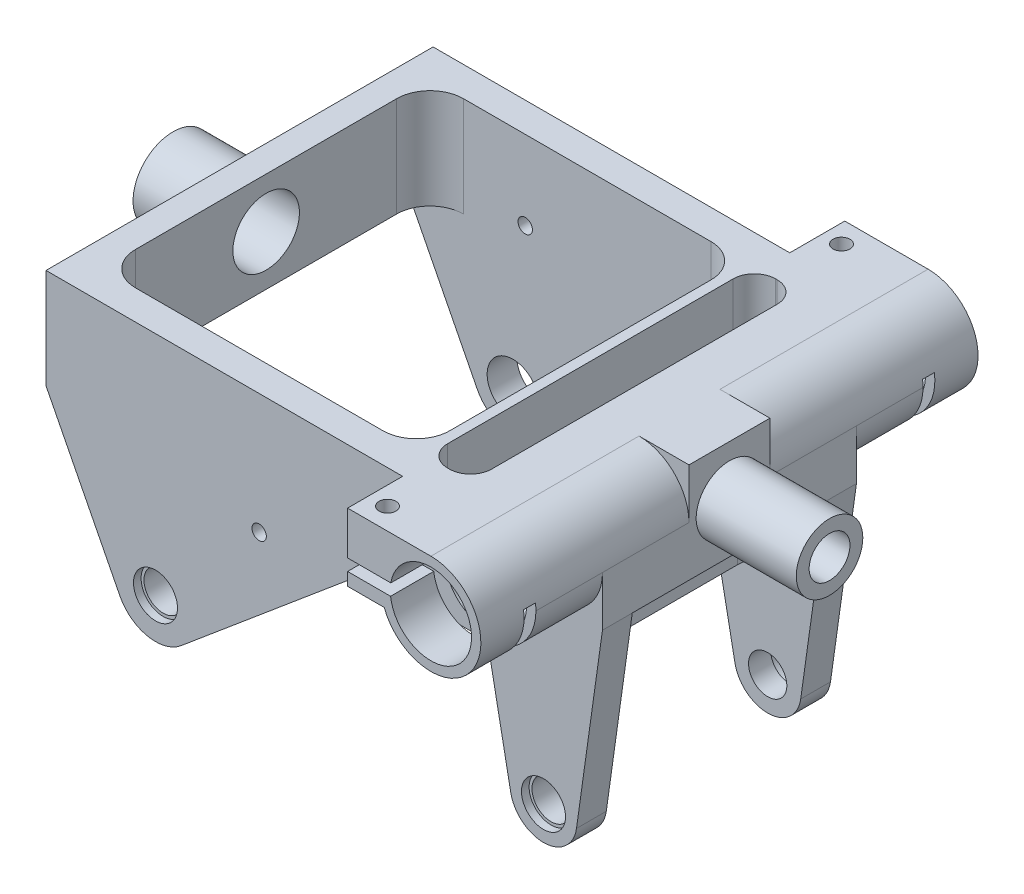
SolidWorks part; units mm, degrees
ref_plane "Front Plane" through (0, 0, 0) normal (0, 0, 1) x (1, 0, 0)
ref_plane "Top Plane" through (0, 0, 0) normal (0, 1, 0) x (1, 0, 0)
ref_plane "Right Plane" through (0, 0, 0) normal (1, 0, 0) x (0, 0, -1)
sketch "Sketch1" plane through (0, 0, 0) normal (0, 1, 0) x (1, 0, 0)
  line L0 (0, 29.0322) -> (0, -29.0322)
  line L1 (0, -29.0322) -> (73.4822, -29.0322)
  line L2 (73.4822, -29.0322) -> (73.4822, 29.0322)
  line L3 (73.4822, 29.0322) -> (0, 29.0322)
  line L4 (3.9878, 19.5872) -> (3.9878, -19.5872)
  line L5 (46.1048, 24.5872) -> (8.9878, 24.5872)
  line L6 (8.9878, -24.5872) -> (46.1048, -24.5872)
  line L7 (51.1048, 19.5872) -> (51.1048, -19.5872)
  line L8 (73.4822, 24.5872) -> (0, 24.5872) construction
  line L9 (3.9878, 29.0322) -> (3.9878, -29.0322) construction
  line L10 (51.1048, 29.0322) -> (51.1048, -29.0322) construction
  line L11 (0, -24.5872) -> (73.4822, -24.5872) construction
  arc A0 (3.9878, -19.5872) -> (8.9878, -24.5872) centre (8.9878, -19.5872) ccw
  arc A1 (46.1048, -24.5872) -> (51.1048, -19.5872) centre (46.1048, -19.5872) ccw
  arc A2 (51.1048, 19.5872) -> (46.1048, 24.5872) centre (46.1048, 19.5872) ccw
  arc A3 (8.9878, 24.5872) -> (3.9878, 19.5872) centre (8.9878, 19.5872) ccw
  dimension "D8" = 5
  dimension "D1" = 58.0644
  dimension "D2" = 29.0322
  dimension "D3" = 73.4822
  dimension "D4" = 3.9878
  dimension "D5" = 4.445
  dimension "D6" = 4.445
  dimension "D7" = 47.117
extrude "Boss-Extrude1" add sketch "Sketch1" against normal blind 46.99
sketch "Sketch2" plane through (0, 0, 0) normal (0, 1, 0) x (1, 0, 0)
  line L0 (51.1048, -19.5872) -> (51.1048, 19.5872) construction
  line L1 (51.1048, -19.5872) -> (51.1048, 19.5872) construction
  line L2 (52.6288, -21.4122) -> (52.6288, 21.4122)
  line L3 (59.2328, -21.4122) -> (59.2328, 21.4122)
  line L4 (55.8038, 24.5872) -> (56.0578, 24.5872)
  line L6 (55.8038, -24.5872) -> (56.0578, -24.5872)
  line L8 (52.6288, -19.5872) -> (52.6288, 19.5872) construction
  line L9 (59.2328, -19.5872) -> (59.2328, 19.5872) construction
  arc A0 (55.8038, -24.5872) -> (52.6288, -21.4122) centre (55.8038, -21.4122) cw
  arc A1 (52.6288, 21.4122) -> (55.8038, 24.5872) centre (55.8038, 21.4122) cw
  arc A2 (56.0578, -24.5872) -> (59.2328, -21.4122) centre (56.0578, -21.4122) ccw
  arc A3 (59.2328, 21.4122) -> (56.0578, 24.5872) centre (56.0578, 21.4122) ccw
  dimension "D3" = 3.175
  dimension "D4" = 3.175
  dimension "D5" = 3.175
  dimension "D1" = 1.524
  dimension "D2" = 6.604
extrude "Cut-Extrude1" cut sketch "Sketch2" against normal blind 14.097
sketch "Sketch3" plane through (0, 0, 0) normal (-1, 0, 0) x (0, 0, 1)
  line L0 (-24.5872, -46.99) -> (-24.5872, 0) construction
  line L1 (-24.5872, -46.99) -> (-24.5872, -14.986)
  line L2 (24.5872, -46.99) -> (24.5872, 0) construction
  line L3 (24.5872, -46.99) -> (24.5872, -14.986)
  line L4 (-24.5872, -14.986) -> (24.5872, -14.986)
  line L7 (-29.0322, 0) -> (29.0322, 0) construction
  line L8 (-29.0322, -46.99) -> (29.0322, -46.99) construction
  line L9 (-24.5872, -46.99) -> (24.5872, -46.99)
  dimension "D1" = 14.986
extrude "Cut-Extrude2" cut sketch "Sketch3" against normal blind 14.097
sketch "Sketch6" plane through (0, 0, 0) normal (-1, 0, 0) x (0, 0, 1)
  line L0 (-29.0322, 0) -> (29.0322, 0) construction
  line L1 (-29.0322, 0) -> (29.0322, 0) construction
  line L2 (24.5872, -14.986) -> (-24.5872, -14.986) construction
  line L3 (24.5872, -14.986) -> (-24.5872, -14.986) construction
  line L4 (0, 0) -> (0, -14.986) construction
  circle A0 centre (0, -7.493) radius 5.9944
  dimension "D1" = 11.9888
extrude "Boss-Extrude3" add sketch "Sketch6" along normal blind 9.9822
sketch "Sketch7" plane through (-9.9822, 0, 0) normal (-1, 0, 0) x (0, 0, 1)
  circle A0 centre (0, -7.493) radius 5.9944 construction
  circle A1 centre (0, -7.493) radius 5.9944 construction
  circle A2 centre (0, -7.493) radius 4.9911
  dimension "D1" = 9.9822
extrude "Cut-Extrude4" cut sketch "Sketch7" against normal blind 15.0622
sketch "Sketch9" plane through (0, -46.99, 0) normal (0, -1, 0) x (1, 0, 0)
  line L0 (51.1048, 0) -> (73.4822, 0) construction
  line L1 (51.1048, 19.5872) -> (51.1048, -19.5872) construction
  line L2 (73.4822, 29.0322) -> (73.4822, -29.0322) construction
  line L3 (70.0913, -14.5796) -> (73.4822, -14.5796)
  line L4 (70.0913, 14.5796) -> (73.4822, 14.5796)
  line L5 (73.4822, 14.5796) -> (73.4822, -14.5796)
  line L6 (65.1002, 9.5885) -> (65.1002, -9.5885)
  line L7 (51.1048, 14.5796) -> (73.4822, 14.5796) construction
  line L8 (65.1002, 29.0322) -> (65.1002, -29.0322) construction
  line L9 (51.1048, -14.5796) -> (73.4822, -14.5796) construction
  line L10 (73.4822, 29.0322) -> (73.4822, -29.0322) construction
  arc A0 (70.0913, -14.5796) -> (65.1002, -9.5885) centre (70.0913, -9.5885) cw
  arc A1 (65.1002, 9.5885) -> (70.0913, 14.5796) centre (70.0913, 9.5885) cw
  dimension "D4" = 4.9911
  dimension "D1" = 14.5796
  dimension "D2" = 14.5796
  dimension "D3" = 8.382
extrude "Cut-Extrude5" cut sketch "Sketch9" against normal blind 32.004
sketch "Sketch10" plane through (0, -46.99, 0) normal (0, -1, 0) x (1, 0, 0)
  line L0 (73.4822, 14.5796) -> (70.0913, 14.5796) construction
  line L1 (58.8137, 14.5796) -> (51.1048, 14.5796)
  line L2 (70.0913, -14.5796) -> (73.4822, -14.5796) construction
  line L3 (51.1048, -14.5796) -> (58.8137, -14.5796)
  line L4 (51.1048, 19.5872) -> (51.1048, -19.5872) construction
  line L5 (51.1048, 14.5796) -> (51.1048, -14.5796)
  line L6 (63.8048, 9.5885) -> (63.8048, -9.5885)
  line L7 (51.1048, 19.5872) -> (51.1048, -19.5872) construction
  line L8 (63.8048, 19.5872) -> (63.8048, -19.5872) construction
  arc A0 (58.8137, -14.5796) -> (63.8048, -9.5885) centre (58.8137, -9.5885) ccw
  arc A1 (63.8048, 9.5885) -> (58.8137, 14.5796) centre (58.8137, 9.5885) ccw
  dimension "D2" = 4.9911
  dimension "D1" = 12.7
extrude "Cut-Extrude6" cut sketch "Sketch10" against normal blind 32.004
sketch "Sketch11" plane through (73.4822, 0, 0) normal (1, 0, 0) x (0, 0, -1)
  line L0 (-14.5796, -14.986) -> (-14.5796, -46.99) construction
  line L1 (-14.5796, -24.9936) -> (-14.5796, -46.99)
  line L2 (14.5796, -14.986) -> (14.5796, -46.99) construction
  line L3 (14.5796, -24.9936) -> (14.5796, -46.99)
  line L4 (-14.5796, -24.9936) -> (14.5796, -24.9936)
  line L5 (-9.5885, -46.99) -> (9.5885, -46.99) construction
  line L6 (-14.5796, -46.99) -> (14.5796, -46.99)
  line L7 (-29.0322, 0) -> (29.0322, 0) construction
  dimension "D1" = 24.9936
extrude "Cut-Extrude7" cut sketch "Sketch11" against normal blind 32.004
sketch "Sketch12" plane through (73.4822, 0, 0) normal (1, 0, 0) x (0, 0, -1)
  line L0 (0, 0) -> (0, -14.986) construction
  line L1 (14.5796, -14.986) -> (-14.5796, -14.986) construction
  circle A0 centre (0, -7.493) radius 4.9911
  circle A1 centre (0, -7.493) radius 3.0607
  dimension "D1" = 6.1214
  dimension "D2" = 9.9822
extrude "Boss-Extrude4" add sketch "Sketch12" along normal blind 15.0114
sketch "Sketch13" plane through (0, 0, 29.0322) normal (0, 0, 1) x (1, 0, 0)
  line L0 (0, 0) -> (73.4822, 0) construction
  line L1 (64.1068, 0) -> (65.9892, 0)
  line L2 (73.4822, -46.99) -> (73.4822, 0) construction
  line L3 (73.4822, -14.8161) -> (73.4822, -7.493)
  line L4 (64.1068, 0) -> (64.1068, 5.1028)
  line L5 (64.1068, 5.1028) -> (76.4375, 5.1028)
  line L6 (76.4375, 5.1028) -> (76.4375, -14.8161)
  line L7 (73.4822, -14.8161) -> (76.4375, -14.8161)
  arc A0 (73.4822, -7.493) -> (65.9892, 0) centre (65.9892, -7.493) ccw
  dimension "D1" = 7.493
extrude "Cut-Extrude8" cut sketch "Sketch13" against normal blind 22.9616
sketch "Sketch14" plane through (0, 0, -29.0322) normal (0, 0, -1) x (-1, 0, 0)
  line L0 (-73.4822, 0) -> (0, 0) construction
  line L1 (-65.9892, 0) -> (-63.3543, 0)
  line L2 (-73.4822, -46.99) -> (-73.4822, 0) construction
  line L3 (-73.4822, -14.062) -> (-73.4822, -7.493)
  line L4 (-63.3543, 0) -> (-63.3543, 2.9537)
  line L5 (-63.3543, 2.9537) -> (-75.6884, 2.9537)
  line L6 (-75.6884, 2.9537) -> (-75.6884, -14.062)
  line L7 (-75.6884, -14.062) -> (-73.4822, -14.062)
  arc A0 (-65.9892, 0) -> (-73.4822, -7.493) centre (-65.9892, -7.493) ccw construction
  arc A1 (-65.9892, 0) -> (-73.4822, -7.493) centre (-65.9892, -7.493) ccw
extrude "Cut-Extrude9" cut sketch "Sketch14" against normal blind 22.9616
sketch "Sketch15" plane through (0, 0, -29.0322) normal (0, 0, -1) x (-1, 0, 0)
  arc A0 (-65.9892, 0) -> (-73.4822, -7.493) centre (-65.9892, -7.493) ccw construction
  arc A1 (-65.9892, 0) -> (-73.4822, -7.493) centre (-65.9892, -7.493) ccw construction
  circle A2 centre (-65.9892, -7.493) radius 6.096
  dimension "D1" = 12.192
extrude "Cut-Extrude10" cut sketch "Sketch15" against normal through all
sketch "Sketch16" plane through (0, 0, 29.0322) normal (0, 0, 1) x (1, 0, 0)
  line L0 (0, -14.986) -> (11.0801, -36.732)
  line L1 (0, -46.99) -> (0, 0) construction
  line L2 (0, 0) -> (65.9892, 0) construction
  line L3 (73.4822, -14.986) -> (70.0913, -14.986) construction
  line L4 (73.4822, -14.986) -> (50.2393, -14.986)
  line L5 (73.4822, -46.99) -> (73.4822, -7.493) construction
  line L6 (73.4822, -49.3823) -> (73.4822, -14.986)
  line L7 (0, -49.3823) -> (0, -14.986)
  line L8 (0, -49.3823) -> (73.4822, -49.3823)
  line L9 (0, 0) -> (65.9892, 0) construction
  line L10 (16.4212, -40.005) -> (65.9892, -40.005) construction
  line L11 (0, -40.005) -> (65.9892, -40.005) construction
  line L12 (16.4212, -34.0106) -> (30.2586, -34.0106) construction
  line L13 (47.0254, -16.1558) -> (20.2743, -38.6026)
  arc A0 (20.2743, -38.6026) -> (11.0801, -36.732) centre (16.4212, -34.0106) cw
  arc A1 (50.2393, -14.986) -> (47.0254, -16.1558) centre (50.2393, -19.986) ccw
  dimension "D3" = 5.9944
  dimension "D5" = 5
  dimension "D1" = 27
  dimension "D2" = 40.005
  dimension "D4" = 77
extrude "Cut-Extrude12" cut sketch "Sketch16" against normal blind 9.9822
fillet "Fillet2" radius 7.493 1 edges at (73.4822, -14.986, 24.0411)
sketch "Sketch17" plane through (0, 0, -29.0322) normal (0, 0, -1) x (-1, 0, 0)
  line L0 (-11.0801, -36.732) -> (0, -14.986) construction
  line L1 (-11.0801, -36.732) -> (0, -14.986)
  line L2 (-51.1048, -14.986) -> (-58.8137, -14.986) construction
  line L3 (-46.1048, -16.9282) -> (-20.2743, -38.6026) construction
  line L4 (0, -46.99) -> (0, 0) construction
  line L5 (-73.4822, -46.99) -> (0, -46.99) construction
  line L6 (-73.4822, -46.99) -> (-73.4822, -7.493) construction
  line L7 (-50.2393, -14.986) -> (-73.4822, -14.986)
  line L8 (-47.0254, -16.1558) -> (-20.2743, -38.6026)
  line L9 (0, -46.99) -> (0, -14.986)
  line L10 (-73.4822, -46.99) -> (0, -46.99)
  line L11 (-73.4822, -46.99) -> (-73.4822, -14.986)
  arc A0 (-47.0254, -16.1558) -> (-50.2393, -14.986) centre (-50.2393, -19.986) ccw construction
  arc A1 (-20.2743, -38.6026) -> (-11.0801, -36.732) centre (-16.4212, -34.0106) ccw construction
  arc A2 (-47.0254, -16.1558) -> (-50.2393, -14.986) centre (-50.2393, -19.986) ccw
  arc A3 (-20.2743, -38.6026) -> (-11.0801, -36.732) centre (-16.4212, -34.0106) ccw
extrude "Cut-Extrude13" cut sketch "Sketch17" against normal blind 9.9822
fillet "Fillet3" radius 7.493 1 edges at (73.4822, -14.986, -24.0411)
sketch "Sketch18" plane through (0, 0, 19.05) normal (0, 0, 1) x (1, 0, 0)
  line L0 (73.4822, -14.986) -> (69.5892, -42.6859)
  line L1 (73.4822, -46.99) -> (73.4822, -7.493) construction
  line L2 (73.4822, -46.99) -> (51.1048, -46.99) construction
  line L3 (64.6379, -46.99) -> (51.1048, -46.99) construction
  line L4 (64.6379, -41.99) -> (64.6379, -36.0159) construction
  line L5 (59.7295, -42.9426) -> (55.139, -19.2891)
  line L6 (51.1048, -46.99) -> (51.1048, -14.986) construction
  line L7 (51.1048, -49.5979) -> (51.1048, -15.3245)
  line L8 (51.1048, -49.5979) -> (73.4822, -49.5979)
  line L9 (73.4822, -49.5979) -> (73.4822, -14.986)
  arc A0 (69.5892, -42.6859) -> (59.7295, -42.9426) centre (64.6379, -41.99) cw
  arc A1 (55.139, -19.2891) -> (51.1048, -15.3245) centre (50.2393, -20.24) ccw
  dimension "D2" = 5
  dimension "D1" = 8
extrude "Cut-Extrude14" cut sketch "Sketch18" against normal up to surface (38.1 mm away) up to face at (63.343, -26.5994, -19.05)
sketch "Sketch19" plane through (0, 0, 29.0322) normal (0, 0, 1) x (1, 0, 0)
  circle A0 centre (16.4212, -34.0106) radius 2.8702
  dimension "D1" = 5.7404
extrude "Cut-Extrude15" cut sketch "Sketch19" against normal through all
sketch "Sketch20" plane through (0, 0, 19.05) normal (0, 0, 1) x (1, 0, 0)
  circle A0 centre (64.6379, -41.99) radius 2.8702
  dimension "D1" = 5.7404
extrude "Cut-Extrude16" cut sketch "Sketch20" against normal through all
sketch "Sketch21" plane through (0, 0, 29.0322) normal (0, 0, 1) x (1, 0, 0)
  line L1 (0, 0) -> (65.9892, 0) construction
  line L2 (53.4924, 0) -> (53.4924, -7.493)
  line L3 (53.4924, 0) -> (53.4924, -6.477)
  line L4 (53.4924, 0) -> (65.9892, 0)
  line L5 (53.4924, -10.16) -> (58.9869, -10.16)
  line L6 (53.4924, -10.16) -> (65.9892, -10.16) construction
  line L7 (53.4924, -8.2296) -> (59.9379, -8.2296)
  line L8 (53.4924, -6.477) -> (59.9785, -6.477)
  line L9 (53.4924, -8.2296) -> (58.9869, -8.2296) construction
  line L10 (53.4924, -6.477) -> (65.9892, -6.477) construction
  line L11 (53.4924, -8.2296) -> (53.4924, -10.16)
  arc A0 (73.4822, -7.493) -> (65.9892, 0) centre (65.9892, -7.493) ccw construction
  arc A1 (73.4822, -7.493) -> (65.9892, 0) centre (65.9892, -7.493) ccw
  arc A2 (65.9892, -14.986) -> (73.4822, -7.493) centre (65.9892, -7.493) ccw construction
  arc A3 (58.9869, -10.16) -> (73.4822, -7.493) centre (65.9892, -7.493) ccw
  circle A4 centre (65.9892, -7.493) radius 6.096 construction
  arc A5 (59.9379, -8.2296) -> (59.9785, -6.477) centre (65.9892, -7.493) ccw
  dimension "D1" = 19.9898
  dimension "D2" = 10.16
  dimension "D3" = 1.9304
  dimension "D4" = 6.477
extrude "Boss-Extrude5" add sketch "Sketch21" along normal blind 8.255
sketch "Sketch22" plane through (0, 0, -29.0322) normal (0, 0, -1) x (-1, 0, 0)
  line L0 (-53.4924, -6.477) -> (-59.9785, -6.477) construction
  line L1 (-59.9379, -8.2296) -> (-53.4924, -8.2296) construction
  line L2 (-53.4924, 0) -> (-53.4924, -6.477) construction
  line L3 (-53.4924, -8.2296) -> (-53.4924, -10.16) construction
  line L4 (-53.4924, -10.16) -> (-58.9869, -10.16) construction
  line L5 (-53.4924, -6.477) -> (-59.9785, -6.477)
  line L6 (-59.9379, -8.2296) -> (-53.4924, -8.2296)
  line L7 (-53.4924, 0) -> (-53.4924, -6.477)
  line L8 (-53.4924, -8.2296) -> (-53.4924, -10.16)
  line L9 (-53.4924, -10.16) -> (-58.9869, -10.16)
  line L10 (-65.9892, 0) -> (0, 0) construction
  line L11 (-65.9892, 0) -> (-53.4924, 0)
  arc A0 (-65.9892, 0) -> (-73.4822, -7.493) centre (-65.9892, -7.493) ccw construction
  circle A1 centre (-65.9892, -7.493) radius 6.096 construction
  arc A2 (-65.9892, -14.986) -> (-58.9869, -10.16) centre (-65.9892, -7.493) ccw construction
  arc A3 (-65.9892, 0) -> (-71.6787, -12.3689) centre (-65.9892, -7.493) ccw
  arc A4 (-59.9785, -6.477) -> (-59.9379, -8.2296) centre (-65.9892, -7.493) ccw
  arc A5 (-71.6787, -12.3689) -> (-58.9869, -10.16) centre (-65.9892, -7.493) ccw
extrude "Boss-Extrude6" add sketch "Sketch22" along normal blind 8.255
sketch "Sketch24" plane through (0, -6.477, 0) normal (0, -1, 0) x (1, 0, 0)
  line L0 (65.9892, 29.0322) -> (50.2393, 29.0322) construction
  line L1 (73.4822, -14.5796) -> (73.4822, 14.5796) construction
  line L2 (50.2393, -29.0322) -> (65.9892, -29.0322) construction
  line L3 (73.4822, 29.0322) -> (50.2393, 29.0322)
  line L4 (73.4822, -30.8102) -> (73.4822, -29.0322)
  line L5 (50.2393, -29.0322) -> (73.4822, -29.0322)
  line L6 (73.4822, 30.8102) -> (50.2393, 30.8102)
  line L7 (50.2393, -30.8102) -> (73.4822, -30.8102)
  line L8 (65.9892, 30.8102) -> (50.2393, 30.8102) construction
  line L9 (50.2393, -30.8102) -> (65.9892, -30.8102) construction
  line L10 (50.2393, -29.0322) -> (65.9892, -29.0322) construction
  line L11 (65.9892, 29.0322) -> (50.2393, 29.0322) construction
  line L12 (73.4822, 29.0322) -> (73.4822, 30.8102)
  line L13 (50.2393, 30.8102) -> (50.2393, 29.0322)
  line L14 (50.2393, -29.0322) -> (50.2393, -30.8102)
  dimension "D1" = 1.778
extrude "Cut-Extrude18" cut sketch "Sketch24" along normal blind 10.795
sketch "Sketch25" plane through (0, -10.16, 0) normal (0, -1, 0) x (1, 0, 0)
  line L0 (56.2397, 37.2872) -> (56.2397, -37.2872) construction
  line L1 (53.4924, 37.2872) -> (58.9869, 37.2872) construction
  line L2 (58.9869, -37.2872) -> (53.4924, -37.2872) construction
  line L3 (58.9869, 34.0487) -> (53.4924, 34.0487) construction
  line L4 (58.9869, 37.2872) -> (58.9869, 30.8102) construction
  line L5 (53.4924, 37.2872) -> (53.4924, 30.8102) construction
  line L6 (58.9869, -34.0487) -> (53.4924, -34.0487) construction
  line L7 (58.9869, -37.2872) -> (58.9869, -30.8102) construction
  line L8 (53.4924, -37.2872) -> (53.4924, -30.8102) construction
  circle A0 centre (56.2397, 34.0487) radius 1.27
  circle A1 centre (56.2397, -34.0487) radius 1.27
  dimension "D1" = 2.54
  dimension "D2" = 2.54
extrude "Cut-Extrude19" cut sketch "Sketch25" against normal through all
sketch "Sketch26" plane through (0, 0, 29.0322) normal (0, 0, 1) x (1, 0, 0)
  circle A0 centre (16.4212, -34.0106) radius 3.302
  dimension "D1" = 6.604
extrude "Cut-Extrude20" cut sketch "Sketch26" against normal blind 1.143
sketch "Sketch27" plane through (0, 0, 19.05) normal (0, 0, 1) x (1, 0, 0)
  circle A0 centre (64.6379, -41.99) radius 3.302
  dimension "D1" = 6.604
extrude "Cut-Extrude21" cut sketch "Sketch27" against normal blind 1.143
sketch "Sketch28" plane through (0, 0, -19.05) normal (0, 0, -1) x (-1, 0, 0)
  circle A0 centre (-64.6379, -41.99) radius 3.302 construction
  circle A1 centre (-64.6379, -41.99) radius 3.302
extrude "Cut-Extrude22" cut sketch "Sketch28" against normal blind 1.143
sketch "Sketch29" plane through (0, 0, -29.0322) normal (0, 0, -1) x (-1, 0, 0)
  circle A0 centre (-16.4212, -34.0106) radius 3.302 construction
  circle A1 centre (-16.4212, -34.0106) radius 3.302
extrude "Cut-Extrude23" cut sketch "Sketch29" against normal blind 1.143
sketch "Sketch30" plane through (0, 0, 29.0322) normal (0, 0, 1) x (1, 0, 0)
  circle A0 centre (31.9714, -18.0278) radius 1.0795
  circle A1 centre (60.8817, -18.0278) radius 1.0795
  circle A2 centre (47.2816, -32.5973) radius 1.0795
  circle A3 centre (34.6256, -32.9935) radius 1.0795
  dimension "D1" = 2.159
extrude "Cut-Extrude24" cut sketch "Sketch30" against normal blind 5.08
sketch "Sketch31" plane through (0, 0, 29.0322) normal (0, 0, 1) x (1, 0, 0)
  line L8 (2.921, -14.986) -> (2.921, 0)
  line L9 (2.921, -13.8173) -> (2.921, 0.6713)
  line L11 (49.6607, -11.1465) -> (33.2013, -24.2152)
  line L14 (27.3416, -28.8677) -> (24.3561, -31.2382)
  line L17 (25.5059, -21.1737) -> (4.0918, -15.3491)
  line L19 (1.5023, -3.279) -> (58.6491, -4.6177)
  arc A0 (21.9945, -30.7893) -> (13.3104, -28.3748) centre (16.4212, -34.0106) ccw
  arc A1 (5.8207, -0.2222) -> (2.9227, -5.495) centre (31.9714, -18.0278) ccw
  arc A2 (57.1764, -5.5269) -> (46.9785, -8.7152) centre (50.6095, -2.4257) ccw
  arc A3 (31.5219, -24.4005) -> (27.9029, -27.274) centre (30.4038, -26.7081) ccw
  arc A4 (17.3256, -25.1435) -> (25.9276, -21.2293) centre (25.9634, -32.7172) ccw
  arc A5 (2.921, -5.4989) -> (19.3187, 10.9689) centre (31.9714, -18.0278) ccw
  arc A6 (49.6607, -11.1465) -> (45.3942, -11.4666) centre (47.2915, -8.1627) ccw
  arc A7 (24.3561, -31.2382) -> (21.9945, -30.7893) centre (23.369, -29.9949) cw
  arc A8 (1.5023, -3.279) -> (2.9227, -5.495) centre (1.4651, -4.8661) ccw
  arc A9 (2.921, 0.6713) -> (5.8207, -0.2222) centre (4.5085, 0.6713) cw
  arc A10 (45.3942, -11.4666) -> (46.9785, -8.7152) centre (46.1847, -10.09) ccw
  arc A11 (57.1764, -5.5269) -> (58.6491, -4.6177) centre (58.6119, -6.2048) ccw
  arc A12 (33.2013, -24.2152) -> (31.5219, -24.4005) centre (32.2141, -22.9719) cw
  arc A13 (27.3416, -28.8677) -> (27.9029, -27.274) centre (26.3545, -27.6244) ccw
  arc A14 (4.0918, -15.3491) -> (2.921, -13.8173) centre (4.5085, -13.8173) cw
  arc A15 (25.9276, -21.2293) -> (25.5059, -21.1737) centre (25.9226, -19.6418) cw
  arc A16 (17.3256, -25.1435) -> (13.3104, -28.3748) centre (6.0882, -15.2905) ccw
  point P23 (0, -2.921)
  point P24 (53.4924, -2.921)
  point P25 (13.6828, -35.4059)
  point P26 (2.6026, -13.6599)
  point P27 (45.1478, -13.9182)
  point P28 (18.3967, -36.365)
  point P53 (28.2702, -28.1304)
  point P58 (25.7198, -21.2318)
  dimension "D2" = 3.81
  dimension "D5" = 1.5875
  dimension "D6" = 1.5875
  dimension "D7" = 1.5875
  dimension "D8" = 1.5875
  dimension "D1" = 2.921
extrude "Cut-Extrude25" cut sketch "Sketch31" against normal blind 3.5052 contours A4 A16 A0 A7 L14 A13 A3 A12 L11 A6 A10 A2 A11 L19 A8 A1 A9 L9 A14 L17 A15 rebuild error yes
sketch "Sketch32" plane through (0, 0, -29.0322) normal (0, 0, -1) x (-1, 0, 0)
  circle A0 centre (-16.4212, -34.0106) radius 3.8735
  dimension "D1" = 7.747
extrude "Cut-Extrude26" cut sketch "Sketch32" against normal blind 5.08
sketch "Sketch33" plane through (0, 0, -29.0322) normal (0, 0, -1) x (-1, 0, 0)
  circle A0 centre (-46.2501, -11.8618) radius 1.0795
  circle A1 centre (-18.2593, -11.8618) radius 1.0795
  dimension "D1" = 2.159
  dimension "D2" = 2.159
extrude "Cut-Extrude27" cut sketch "Sketch33" against normal blind 5.08
sketch "Sketch34" plane through (0, 0, -29.0322) normal (0, 0, -1) x (-1, 0, 0)
  line L0 (-33.4584, -24.011) -> (-33.2013, -24.2152) construction
  line L1 (-50.7694, -9.2011) -> (-39.9757, -18.2581)
  line L2 (-3.4126, -3.3238) -> (-36.7702, -4.1052) construction
  line L3 (-2.921, -9.5803) -> (-2.921, -5.4989) construction
  line L4 (-26.1709, -21.3545) -> (-4.6644, -15.5048) construction
  line L5 (-4.5085, -2.921) -> (-48.4837, -2.921)
  line L6 (-2.921, -13.9036) -> (-2.921, -4.5085)
  line L7 (-10.3074, -28.7814) -> (-8.2734, -24.7895)
  line L8 (-33.6432, -23.5717) -> (-24.0922, -31.5859)
  line L9 (-4.5005, -17.3847) -> (-3.094, -14.6243)
  arc A0 (-33.9752, -21.5243) -> (-37.9017, -18.2295) centre (-36.1824, -20.1676) ccw
  arc A1 (-6.78, -17.9952) -> (-9.1194, -22.5866) centre (-8.1916, -20.1676) ccw
  arc A2 (-15.6695, -27.6173) -> (-21.9945, -30.7893) centre (-16.4212, -34.0106) ccw construction
  arc A3 (-12.7058, -29.3065) -> (-21.6793, -31.1321) centre (-16.4212, -34.0106) ccw
  arc A4 (-4.5085, -2.921) -> (-2.921, -4.5085) centre (-4.5085, -4.5085) cw
  arc A5 (-2.921, -13.9036) -> (-3.094, -14.6243) centre (-4.5085, -13.9036) cw
  arc A6 (-10.3074, -28.7814) -> (-12.7058, -29.3065) centre (-11.7218, -28.0607) cw
  arc A7 (-21.6793, -31.1321) -> (-24.0922, -31.5859) centre (-23.0718, -30.3698) cw
  arc A8 (-48.4837, -2.921) -> (-50.7694, -9.2011) centre (-48.4837, -6.477) ccw
  arc A9 (-4.5005, -17.3847) -> (-6.78, -17.9952) centre (-5.915, -16.664) cw
  arc A10 (-9.1194, -22.5866) -> (-8.2734, -24.7895) centre (-9.6879, -24.0688) cw
  arc A11 (-33.6432, -23.5717) -> (-33.9752, -21.5243) centre (-32.6228, -22.3556) cw
  arc A12 (-37.9017, -18.2295) -> (-39.9757, -18.2581) centre (-38.9552, -17.042) cw
  point P36 (-5.6535, -19.6476)
  point P41 (-34.9708, -22.4577)
  dimension "D1" = 5.1816
  dimension "D2" = 5.1816
  dimension "D3" = 1.5875
  dimension "D4" = 3.556
  dimension "D5" = 1.5875
extrude "Cut-Extrude28" cut sketch "Sketch34" against normal blind 2.54
scale "Scale1" scale about centroid uniform scaling yes scale factor 0.6
